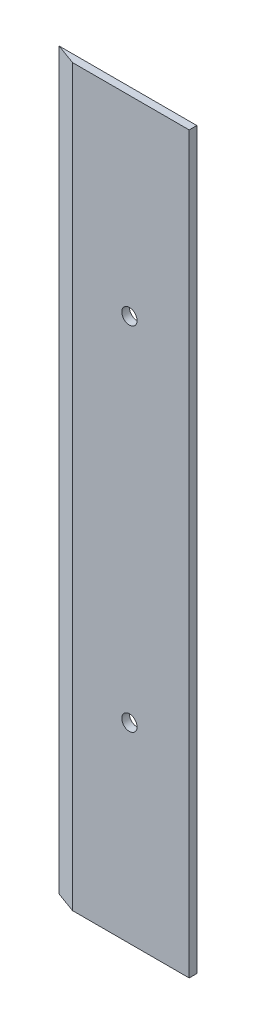
SolidWorks part; units mm, degrees
ref_plane "Спереди" through (0, 0, 0) normal (0, 0, 1) x (1, 0, 0)
ref_plane "Сверху" through (0, 0, 0) normal (0, 1, 0) x (1, 0, 0)
ref_plane "Справа" through (0, 0, 0) normal (1, 0, 0) x (0, 0, -1)
sketch "Эскиз1" plane through (0, 0, 0) normal (0, 0, 1) x (1, 0, 0)
  line L1 (-48.4463, 48) -> (-66.4463, 48)
  line L2 (-48.4463, 48) -> (-48.4463, -48)
  line L3 (-48.4463, -48) -> (-66.4463, -48)
  line L4 (-66.4463, 48) -> (-66.4463, -48)
  circle A0 centre (-56.2632, 23) radius 1
  circle A1 centre (-56.2632, -23) radius 1
extrude "Бобышка-Вытянуть1" add sketch "Эскиз1" along normal blind 1 contours L1 L4 L3 L2 A1 A0 region at (-57.4506, 0, 0)
sketch "Эскиз2" plane through (0, 48, 0) normal (0, 1, 0) x (1, 0, 0)
  line L0 (-66.4463, 0) -> (-63.6988, -1)
  line L1 (-48.4463, -1) -> (-66.4463, -1) construction
  line L2 (-48.4463, 0) -> (-66.4463, 0) construction
  line L4 (-63.6988, -1) -> (-66.4463, -1)
  line L5 (-66.4463, -1) -> (-66.4463, 0)
  dimension "D1" = 20
extrude "Вырез-Вытянуть1" cut sketch "Эскиз2" against normal through all
